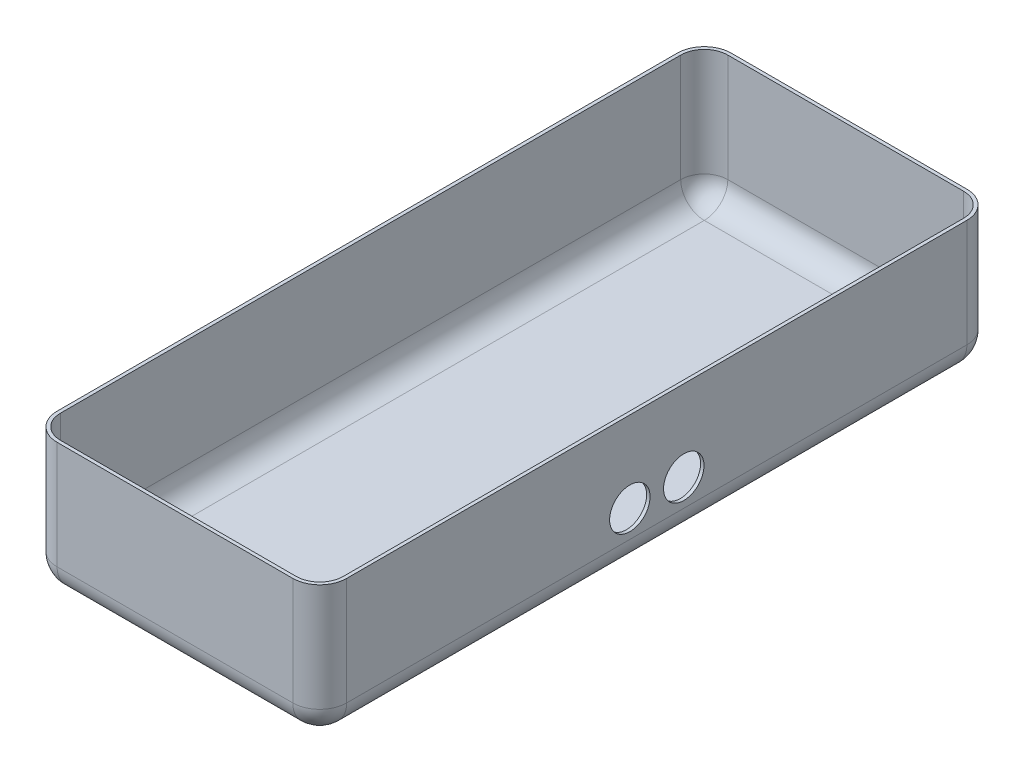
SolidWorks part; units mm, degrees
material "McMaster 6061-T6"
ref_plane "Front" through (0, 0, 0) normal (0, 0, 1) x (1, 0, 0)
ref_plane "Top" through (0, 0, 0) normal (0, 1, 0) x (1, 0, 0)
ref_plane "Right" through (0, 0, 0) normal (1, 0, 0) x (0, 0, -1)
sketch "Sketch1" plane through (0, 0, 0) normal (0, 1, 0) x (1, 0, 0)
  line L1 (0, 0) -> (136.398, 0)
  line L2 (0, 0) -> (0, 317.5)
  line L3 (0, 317.5) -> (136.398, 317.5)
  line L4 (136.398, 0) -> (136.398, 317.5)
  dimension "D1" = 136.398
  dimension "D2" = 317.5
extrude "Boss-Extrude1" add sketch "Sketch1" along normal blind 63.5
fillet "Fillet1" radius 12.7 8 edges at (0, 0, -158.75) (0, 31.75, -317.5) (68.199, 0, -317.5) (136.398, 31.75, -317.5) (68.199, 0, 0) (136.398, 0, -158.75) (136.398, 31.75, 0) (0, 31.75, 0)
shell "Shell1" thickness 1.6002 removed face at (68.199, 63.5, -158.75)
sketch "Sketch2" plane through (136.398, 0, 0) normal (1, 0, 0) x (0, 0, -1)
  line L0 (12.7, 25.4) -> (146.05, 25.4) construction
  line L2 (12.7, 63.5) -> (12.7, 12.7) construction
  line L3 (146.05, 25.4) -> (171.45, 25.4) construction
  line L4 (171.45, 25.4) -> (304.8, 25.4) construction
  line L6 (304.8, 12.7) -> (304.8, 63.5) construction
  line L8 (12.7, 12.7) -> (304.8, 12.7) construction
  circle A1 centre (146.05, 25.4) radius 9.525
  circle A3 centre (171.45, 25.4) radius 9.525
  point P0 (213.5597, 27.2575)
  point P14 (230.2123, 25.4)
  dimension "D1" = 19.05
  dimension "D2" = 12.7
  dimension "D3" = 25.4
extrude "Cut-Extrude1" cut sketch "Sketch2" against normal up to next
